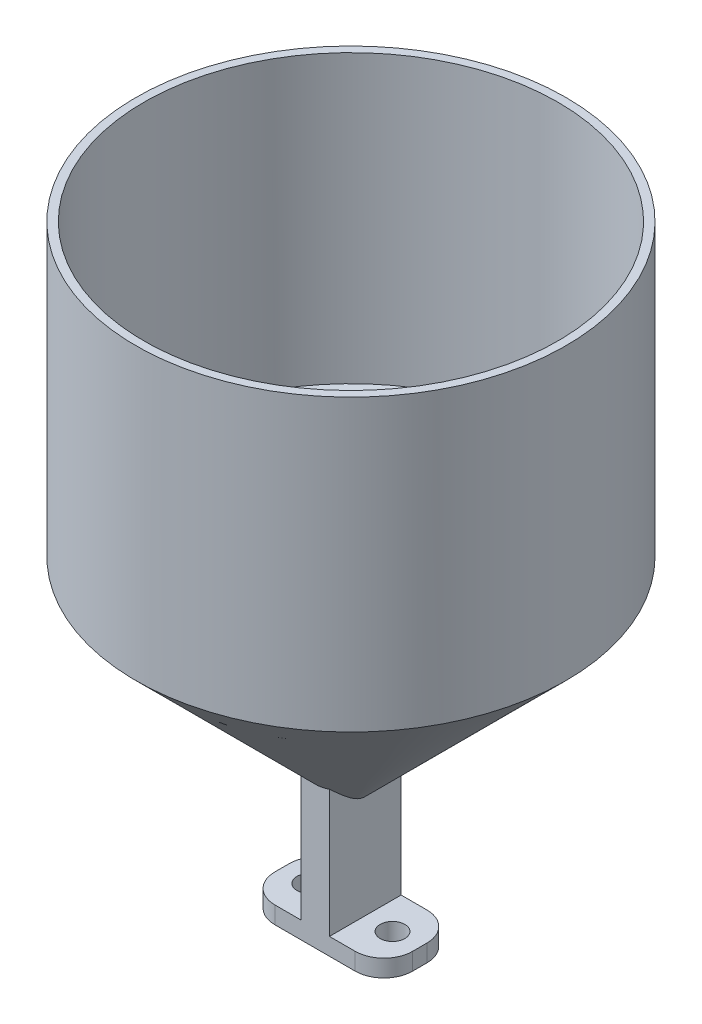
SolidWorks part; units mm, degrees
material "ABS"
ref_plane "Front Plane" through (0, 0, 0) normal (0, 0, 1) x (1, 0, 0)
ref_plane "Top Plane" through (0, 0, 0) normal (0, 1, 0) x (1, 0, 0)
ref_plane "Right Plane" through (0, 0, 0) normal (1, 0, 0) x (0, 0, -1)
sketch "Sketch1" plane through (0, 0, 0) normal (0, 1, 0) x (1, 0, 0)
  line L0 (-7.25, 0) -> (7.25, 0) construction
  line L2 (-2.5, -6.25) -> (2.5, -6.25) construction
  line L3 (-2.5, -6.25) -> (-2.5, 6.25) construction
  line L4 (-2.5, 6.25) -> (2.5, 6.25) construction
  line L5 (2.5, -6.25) -> (2.5, 6.25) construction
  line L6 (-2.5, -6.25) -> (2.5, 6.25) construction
  line L7 (-2.5, 6.25) -> (2.5, -6.25) construction
  line L8 (-7, -6.25) -> (7, -6.25)
  line L9 (-12, -1.25) -> (-12, 1.25)
  line L10 (-7, 6.25) -> (7, 6.25)
  line L11 (12, -1.25) -> (12, 1.25)
  line L12 (-12, -6.25) -> (12, 6.25) construction
  line L13 (-12, 6.25) -> (12, -6.25) construction
  circle A0 centre (-7.25, 0) radius 2.15
  circle A1 centre (7.25, 0) radius 2.15
  circle A2 centre (-7.25, 0) radius 4.75 construction
  circle A3 centre (7.25, 0) radius 4.75 construction
  arc A4 (-7, -6.25) -> (-12, -1.25) centre (-7, -1.25) cw
  arc A5 (7, -6.25) -> (12, -1.25) centre (7, -1.25) ccw
  arc A6 (7, 6.25) -> (12, 1.25) centre (7, 1.25) cw
  arc A7 (-12, 1.25) -> (-7, 6.25) centre (-7, 1.25) cw
  point P4 (0, 0)
  point P9 (0, 0)
  point P14 (0, 0)
  dimension "D1" = 4.3
  dimension "D3" = 9.5
  dimension "D5" = 5
  dimension "D2" = 14.5
  dimension "D4" = 12.5
extrude "Boss-Extrude1" add sketch "Sketch1" along normal mid plane 3
sketch "Sketch3" plane through (0, 0, 6.25) normal (0, 0, 1) x (1, 0, 0)
  line L0 (-7, 1.5) -> (7, 1.5) construction
  line L1 (-2.5, 21.5) -> (2.5, 21.5) construction
  line L2 (-2.5, 21.5) -> (-2.5, 1.5) construction
  line L3 (-2.5, 1.5) -> (2.5, 1.5) construction
  line L4 (2.5, 21.5) -> (2.5, 1.5) construction
  line L5 (-2.5, 21.5) -> (2.5, 1.5) construction
  line L6 (-2.5, 1.5) -> (2.5, 21.5) construction
  line L8 (-12, 1.5) -> (-12, -1.5) construction
  line L9 (-2.5, 1.5) -> (-12, 1.5) construction
  line L10 (-2.5, 21.5) -> (2.5, 21.5)
  line L11 (-4.5, 17) -> (-12, 17) construction
  line L12 (-4.5, 17) -> (-4.5, 21.5) construction
  line L13 (-4.5, 21.5) -> (-12, 21.5) construction
  line L14 (-12, 17) -> (-12, 21.5) construction
  line L15 (-4.5, 17) -> (-12, 21.5) construction
  line L16 (-4.5, 21.5) -> (-12, 17) construction
  line L17 (-2.5, 1.5) -> (-2.5, 21.5)
  line L18 (-2.5, 1.5) -> (-12, 1.5) construction
  line L19 (-2.5, 1.5) -> (-2.5, 6.5) construction
  line L20 (-2.5, 6.5) -> (-12, 6.5) construction
  line L21 (-12, 1.5) -> (-12, 6.5) construction
  line L22 (-2.5, 1.5) -> (-12, 6.5) construction
  line L23 (-2.5, 6.5) -> (-12, 1.5) construction
  line L24 (0, 0) -> (0, 32.0144) construction
  line L25 (2.5, 21.5) -> (2.5, 1.5)
  line L26 (2.5, 1.5) -> (-2.5, 1.5)
  point P0 (0, 11.5)
  point P7 (-8.25, 19.25)
  point P11 (-7.25, 4)
  point P13 (0, 21.5)
  dimension "D1" = 9.5
  dimension "D2" = 20
  dimension "D3" = 7.5
  dimension "D4" = 4.5
  dimension "D5" = 5
extrude "Boss-Extrude3" add sketch "Sketch3" against normal up to surface (12.5 mm away) up to face at (0, 0, -6.25)
sketch "Sketch4" plane through (0, 0, 0) normal (0, 0, 1) x (1, 0, 0)
  line L0 (-2.5, 19.5) -> (-37.5, 54.5)
  line L1 (-2.5, 1.5) -> (-2.5, 21.5) construction
  line L4 (-36.0858, 55.0858) -> (-37.0858, 54.0858) construction
  line L7 (-2.5, 21.5) -> (0, 21.5)
  line L8 (0, -200000) -> (0, 200032.0144) construction
  line L9 (-2.5, 19.5) -> (0, 19.5)
  line L11 (0, 0) -> (0, 34.2554) construction
  line L12 (-37.5, 54.5) -> (-37.5, 105.0858)
  line L13 (-37.5, 105.0858) -> (-36.0858, 105.0858)
  line L14 (-36.0858, 105.0858) -> (-36.0858, 55.0858)
  line L15 (-36.0858, 55.0858) -> (-2.5, 21.5)
  line L16 (0, 21.5) -> (0, 19.5)
  dimension "D1" = 45
  dimension "D2" = 75
  dimension "D4" = 50
revolve "Revolve1" add sketch "Sketch4" angle 360 about L11
sketch "Sketch5" plane through (0, 21.5, 0) normal (0, 1, 0) x (1, 0, 0)
  line L6 (2.5, -6.25) -> (2.5, -3.7417)
  line L7 (-2.5, -3.7417) -> (-2.5, -6.25)
  line L8 (-2.5, -6.25) -> (2.5, -6.25)
  line L9 (2.5, -6.25) -> (2.5, -3.7417)
  line L10 (-2.5, -3.7417) -> (-2.5, -6.25)
  line L11 (-2.5, -6.25) -> (2.5, -6.25)
  line L15 (-2.5, 6.25) -> (-2.5, 3.7417)
  line L16 (2.5, 3.7417) -> (2.5, 6.25)
  line L17 (2.5, 6.25) -> (-2.5, 6.25)
  line L18 (-2.5, 6.25) -> (-2.5, 3.7417)
  line L19 (2.5, 3.7417) -> (2.5, 6.25)
  line L20 (2.5, 6.25) -> (-2.5, 6.25)
  arc A2 (-2.5, -3.7417) -> (2.5, -3.7417) centre (0, 0) ccw
  arc A3 (-2.5, -3.7417) -> (2.5, -3.7417) centre (0, 0) ccw
  arc A5 (2.5, 3.7417) -> (-2.5, 3.7417) centre (0, 0) ccw
  arc A6 (2.5, 3.7417) -> (-2.5, 3.7417) centre (0, 0) ccw
  dimension "D1" = 0
  dimension "D2" = 0
extrude "Boss-Extrude4" add sketch "Sketch5" along normal up to next
